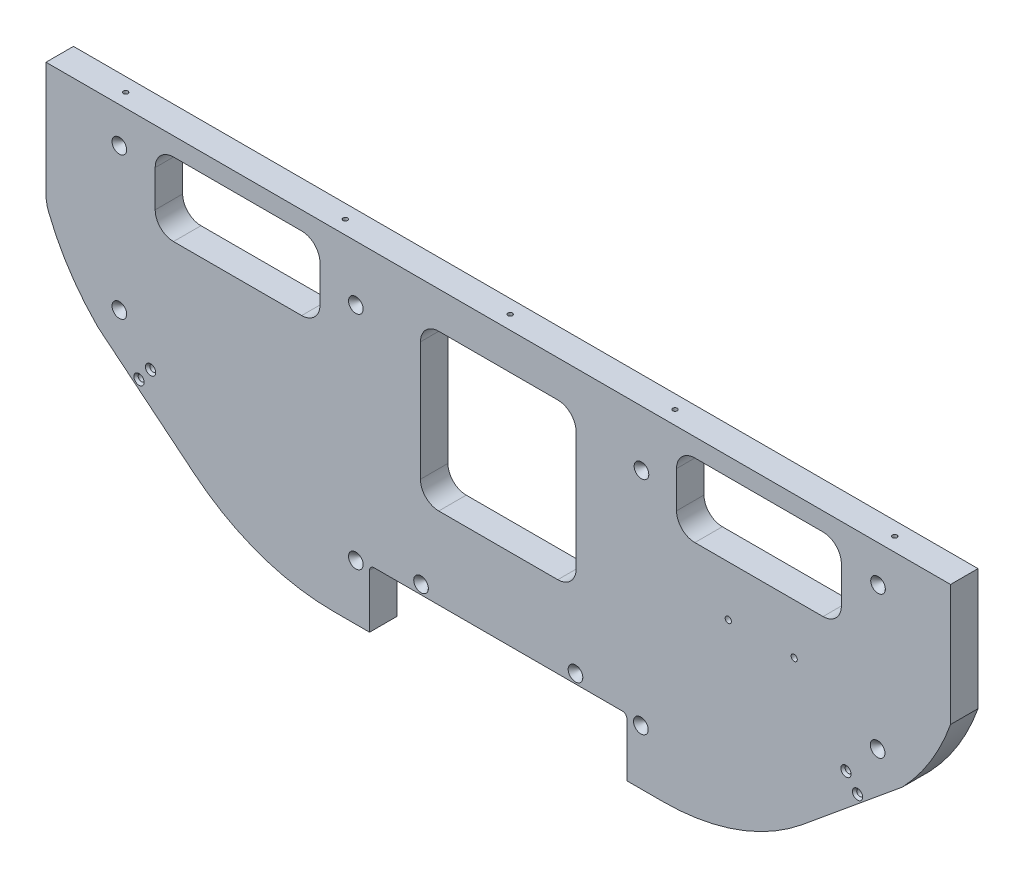
SolidWorks part; units mm, degrees
material "MDF"
ref_plane "Front Plane" through (0, 0, 0) normal (0, 0, 1) x (1, 0, 0)
ref_plane "Top Plane" through (0, 0, 0) normal (0, 1, 0) x (1, 0, 0)
ref_plane "Right Plane" through (0, 0, 0) normal (1, 0, 0) x (0, 0, -1)
sketch "Sketch1" plane through (0, 0, 0) normal (0, 0, 1) x (1, 0, 0)
  line L0 (-394.3668, -87.3125) -> (-394.3668, 23.8125) construction
  line L2 (-618.7885, -233.3625) -> (-593.7568, -233.3625) construction
  line L3 (-394.3668, -87.3125) -> (-394.3668, -3.175)
  line L4 (-497.3744, -199.0142) -> (-427.7551, -141.5981)
  line L5 (-709.3268, -233.3625) -> (-593.7568, -233.3625)
  line L6 (-709.3268, -3.175) -> (-709.3268, -233.3625) construction
  line L7 (-1021.7468, -3.175) -> (-396.9068, -3.175) construction
  line L8 (-394.3668, -3.175) -> (-709.3268, -3.175)
  line L9 (-1021.7468, -3.175) -> (-396.9068, -3.175) construction
  line L10 (-976.0268, -152.2395) -> (-918.7391, -199.0142) construction
  line L11 (-1021.7467, -87.3125) -> (-1021.7467, -20.955) construction
  line L12 (-985.5517, -144.4625) -> (-918.7391, -199.0142)
  line L13 (-1021.7467, -87.3125) -> (-1021.7468, -3.175)
  line L14 (-822.3567, -233.3625) -> (-709.3268, -233.3625)
  line L15 (-709.3268, -3.175) -> (-1021.7468, -3.175)
  arc A0 (-427.7551, -141.5981) -> (-394.3668, -87.3125) centre (-538.0037, -36.3792) ccw construction
  arc A1 (-593.7568, -233.3625) -> (-497.3744, -199.0142) centre (-593.7568, -80.9625) ccw construction
  arc A2 (-427.7551, -141.5981) -> (-394.3668, -87.3125) centre (-538.0037, -36.3792) ccw
  arc A3 (-593.7568, -233.3625) -> (-497.3744, -199.0142) centre (-593.7568, -80.9625) ccw
  arc A4 (-918.7391, -199.0142) -> (-822.3567, -233.3625) centre (-822.3567, -80.9625) ccw construction
  arc A5 (-1021.7467, -87.3125) -> (-985.5517, -144.4625) centre (-878.1098, -36.3792) ccw construction
  arc A6 (-918.7391, -199.0142) -> (-822.3567, -233.3625) centre (-822.3567, -80.9625) ccw
  arc A7 (-1021.7467, -87.3125) -> (-985.5517, -144.4625) centre (-878.1098, -36.3792) ccw
  point P13 (-709.3268, -3.175)
extrude "Boss-Extrude1" add sketch "Sketch1" along normal blind 19.05
hole_wizard "5/64 (0.07813) Diameter Hole1" positions "Sketch2" profile "Sketch3" hole size "5/64" standard "ANSI Inch"
sketch "Sketch2" plane through (-708.0567, 15.875, 6128.5599) normal (0, 1, 0) x (1, 0, 0)
  line L1 (-1.27, 6109.5099) -> (-1.27, 6338.7449) construction
  point P0 (-262.8265, 6157.4524)
  point P6 (-98.7933, 6157.4524)
  point P18 (-262.8265, 6233.6524)
  point P19 (-98.7933, 6233.6524)
  point P22 (-262.8265, 6309.8524)
  point P23 (-98.7933, 6309.8524)
  point P24 (-267.97, 6119.0349)
  point P34 (-115.57, 6119.0349)
  point P37 (-1.27, 6119.0349)
  point P40 (113.03, 6119.0349)
  point P44 (265.43, 6119.0349)
  point P55 (96.2533, 6309.8524)
  point P56 (260.2865, 6309.8524)
  point P59 (96.2533, 6233.6524)
  point P60 (260.2865, 6233.6524)
  point P63 (96.2533, 6157.4524)
  point P64 (260.2865, 6157.4524)
sketch "Sketch3" plane through (-970.8832, 15.875, -28.8925) normal (1, 0, 0) x (0, 0, 1)
  line L0 (0, 0) -> (0, 39.0539)
  line L1 (0, 39.0539) -> (1.5875, 38.1)
  line L2 (1.5875, 38.1) -> (1.5875, 4.0177)
  line L3 (1.5875, 4.0177) -> (5.08, 0)
  line L4 (5.08, 0) -> (0, 0)
  line L5 (-1.5875, 4.0177) -> (-5.08, 0) construction
  line L6 (0, 39.0539) -> (-1.5875, 38.1) construction
  line L7 (0, -6.35) -> (0, 107.95) construction
  dimension "Hole Dia." = 3.175
  dimension "Hole Depth" = 38.1
  dimension "Near C'Sink Dia." = 10.16
  dimension "Near C'Sink Angle" = 82
  dimension "Drill Angle" = 118
hole_wizard "5/64 (0.07813) Diameter Hole2" positions "Sketch4" profile "Sketch5" hole size "5/64" standard "ANSI Inch"
sketch "Sketch4" plane through (-708.0567, 1936.854, 19.05) normal (0, 0, 1) x (-1, 0, 0)
  line L23 (262.8265, 2088.1084) -> (262.8265, 2038.7486)
  line L24 (262.8265, 2038.7486) -> (262.8265, 1989.3888)
  line L25 (262.8265, 1989.3888) -> (262.8265, 2038.7486)
  line L26 (262.8265, 2038.7486) -> (262.8265, 1989.3888)
  line L27 (262.8265, 1989.3888) -> (262.8265, 1940.029)
  line L33 (98.7933, 2170.2165) -> (98.7933, 2131.8519)
  line L35 (98.7933, 2131.8519) -> (98.7933, 2093.4873)
  line L36 (98.7933, 2093.4873) -> (98.7933, 2055.1227)
  line L37 (98.7933, 2055.1227) -> (98.7933, 2016.7581)
  line L38 (98.7933, 2016.7581) -> (98.7933, 1978.3935)
  line L39 (98.7933, 1978.3935) -> (98.7933, 1940.029)
  line L44 (89.2683, 2123.544) -> (53.561, 2123.544)
  line L46 (53.561, 2123.544) -> (17.8537, 2123.544)
  line L47 (17.8537, 2123.544) -> (-17.8537, 2123.544)
  line L48 (-17.8537, 2123.544) -> (-53.561, 2123.544)
  line L49 (-53.561, 2123.544) -> (-89.2683, 2123.544)
  line L53 (0, 2170.2165) -> (-0.3175, 1940.029) construction
  line L55 (-99.3221, 1978.6668) -> (-99.4279, 1940.3024)
  line L56 (-99.2163, 2017.0312) -> (-99.3221, 1978.6668)
  line L57 (-99.1104, 2055.3957) -> (-99.2163, 2017.0312)
  line L58 (-99.0046, 2093.7601) -> (-99.1104, 2055.3957)
  line L59 (-98.8988, 2132.1245) -> (-99.0046, 2093.7601)
  line L60 (-98.7929, 2170.489) -> (-98.8988, 2132.1245)
  line L61 (-263.3243, 1990.1145) -> (-263.4605, 1940.7549)
  line L62 (-263.1882, 2039.4741) -> (-263.3243, 1990.1145)
  line L63 (-263.3243, 1990.1145) -> (-263.1882, 2039.4741)
  line L64 (-263.1882, 2039.4741) -> (-263.3243, 1990.1145)
  line L65 (-263.052, 2088.8338) -> (-263.1882, 2039.4741)
  point P71 (262.8265, 1964.7089)
  point P79 (262.8265, 2063.4285)
  point P95 (98.7933, 2131.8519)
  point P103 (98.7933, 1978.3935)
  point P126 (53.561, 2123.544)
  point P134 (-53.561, 2123.544)
  point P162 (-99.3221, 1978.6668)
  point P166 (-98.8988, 2132.1245)
  point P167 (-263.1201, 2064.1539)
  point P169 (-263.3924, 1965.4347)
sketch "Sketch5" plane through (-444.6643, -28.5807, 19.05) normal (1, 0, 0) x (0, -1, 0)
  line L0 (0, 0) -> (0, 38.6962)
  line L1 (0, 38.6962) -> (0.9923, 38.1)
  line L2 (0.9923, 38.1) -> (0.9923, 4.7024)
  line L3 (0.9923, 4.7024) -> (5.08, 0)
  line L4 (5.08, 0) -> (0, 0)
  line L5 (-0.9923, 4.7024) -> (-5.08, 0) construction
  line L6 (0, 38.6962) -> (-0.9923, 38.1) construction
  line L7 (0, -6.35) -> (0, 107.95) construction
  dimension "Hole Dia." = 1.9845
  dimension "Hole Depth" = 38.1
  dimension "Near C'Sink Dia." = 10.16
  dimension "Near C'Sink Angle" = 82
  dimension "Drill Angle" = 118
sketch "Sketch6" plane through (0, 0, 0) normal (0, 0, -1) x (-1, 0, 0)
  line L1 (797.325, -233.3625) -> (618.7884, -233.3625)
  line L2 (797.325, -233.3625) -> (797.325, -193.04)
  line L3 (797.325, -193.04) -> (618.7884, -193.04)
  line L4 (618.7884, -233.3625) -> (618.7884, -193.04)
extrude "Cut-Extrude1" cut sketch "Sketch6" against normal up to next
fillet "Fillet1" radius 25.4 2 edges at (-985.5517, -144.4625, 9.525) (-1021.7467, -87.3125, 9.525)
hole_wizard "#6 Clearance Hole1" positions "Sketch7" profile "Sketch8" hole size "#6" standard "ANSI Inch" end condition up to next
sketch "Sketch7" plane through (0, 0, 19.05) normal (0, 0, 1) x (1, 0, 0)
  arc A0 (-504.7297, -98.0667) -> (-504.7297, -104.8742) centre (-502.7993, -101.4705) ccw construction
  arc A1 (-550.4497, -98.0667) -> (-550.4497, -104.8742) centre (-548.5193, -101.4705) ccw construction
  point P0 (-502.7993, -101.4705)
  point P2 (-548.5193, -101.4705)
sketch "Sketch8" plane through (-502.7993, -101.4705, 19.05) normal (1, 0, 0) x (0, -1, 0)
  line L0 (0, 0) -> (0, 19.05)
  line L1 (0, 19.05) -> (2.1526, 19.05)
  line L2 (2.1526, 19.05) -> (2.1526, 0)
  line L5 (2.1526, 0) -> (0, 0)
  line L11 (0, -6.35) -> (0, 107.95) construction
  dimension "Thru Hole Dia." = 4.3053
  dimension "Thru Hole Depth" = 19.05
hole_wizard "CSK for #6 Flat Head Machine Screw (100)1" positions "Sketch9" profile "Sketch10" countersink size "#6" standard "ANSI Inch" end condition up to next
sketch "Sketch9" plane through (0, 0, 19.05) normal (0, 0, 1) x (1, 0, 0)
  point P0 (-957.2382, -161.4319)
  point P3 (-949.206, -151.5944)
  point P6 (-466.9052, -151.5924)
  point P9 (-458.8731, -161.4298)
sketch "Sketch10" plane through (-957.2382, -161.4319, 19.05) normal (1, 0, 0) x (0, -1, 0)
  line L0 (0, 0) -> (0, 19.05)
  line L1 (0, 19.05) -> (2.1526, 19.05)
  line L2 (2.1526, 19.05) -> (2.1526, 1.5998)
  line L3 (2.1526, 1.5998) -> (3.5433, 0)
  line L5 (3.5433, 0) -> (0, 0)
  line L6 (-2.1526, 1.5998) -> (-3.5433, 0) construction
  line L11 (0, -6.35) -> (0, 107.95) construction
  dimension "Thru Hole Dia." = 4.3053
  dimension "Thru Hole Depth" = 19.05
  dimension "Near C'Sink Dia." = 7.0866
  dimension "Near C'Sink Angle" = 82
sketch "Sketch12" plane through (0, 0, 19.05) normal (0, 0, 1) x (1, 0, 0)
  line L0 (-708.0568, -193.04) -> (-708.0568, -3.175) construction
  line L1 (-797.325, -193.04) -> (-618.7884, -193.04) construction
  line L2 (-394.3668, -3.175) -> (-1021.7468, -3.175) construction
  line L3 (-970.8832, -27.8549) -> (-806.85, -27.8549) construction
  line L4 (-806.85, -41.5396) -> (-806.85, -27.8549) construction
  line L5 (-584.3969, -15.875) -> (-470.0969, -15.875)
  line L6 (-831.7166, -66.675) -> (-946.0166, -66.675)
  line L7 (-831.7166, -66.675) -> (-831.7166, -15.875)
  line L8 (-831.7166, -15.875) -> (-946.0166, -15.875)
  line L9 (-946.0166, -66.675) -> (-946.0166, -15.875)
  line L10 (-831.7166, -66.675) -> (-946.0166, -15.875) construction
  line L11 (-831.7166, -15.875) -> (-946.0166, -66.675) construction
  line L12 (-470.0969, -66.675) -> (-470.0969, -15.875)
  line L13 (-584.3969, -66.675) -> (-470.0969, -66.675)
  line L14 (-584.3969, -66.675) -> (-584.3969, -15.875)
  line L15 (-394.3668, -3.175) -> (-1021.7468, -3.175) construction
  line L16 (-654.0818, -136.525) -> (-762.0318, -136.525)
  line L17 (-654.0818, -136.525) -> (-654.0818, -28.575)
  line L18 (-654.0818, -28.575) -> (-762.0318, -28.575)
  line L19 (-762.0318, -136.525) -> (-762.0318, -28.575)
  line L20 (-654.0818, -136.525) -> (-762.0318, -28.575) construction
  line L21 (-654.0818, -28.575) -> (-762.0318, -136.525) construction
  point P9 (-888.8666, -27.8549)
  point P10 (-888.8666, -41.275)
  point P20 (-708.0568, -82.55)
  dimension "D1" = 114.3
  dimension "D2" = 50.8
  dimension "D3" = 12.7
  dimension "D4" = 107.95
  dimension "D5" = 107.95
  dimension "D6" = 25.4
extrude "Cut-Extrude2" cut sketch "Sketch12" against normal through all
fillet "Fillet2" radius 12.7 12 edges at (-584.3969, -66.675, 9.525) (-584.3969, -15.875, 9.525) (-470.0969, -15.875, 9.525) (-470.0969, -66.675, 9.525) (-654.0818, -136.525, 9.525) (-654.0818, -28.575, 9.525) (-762.0318, -28.575, 9.525) (-762.0318, -136.525, 9.525) (-946.0166, -66.675, 9.525) (-946.0166, -15.875, 9.525) (-831.7166, -15.875, 9.525) (-831.7166, -66.675, 9.525)
fillet "Fillet3" radius 3.175 2 edges at (-618.7884, -193.04, 9.525) (-797.325, -193.04, 9.525)
